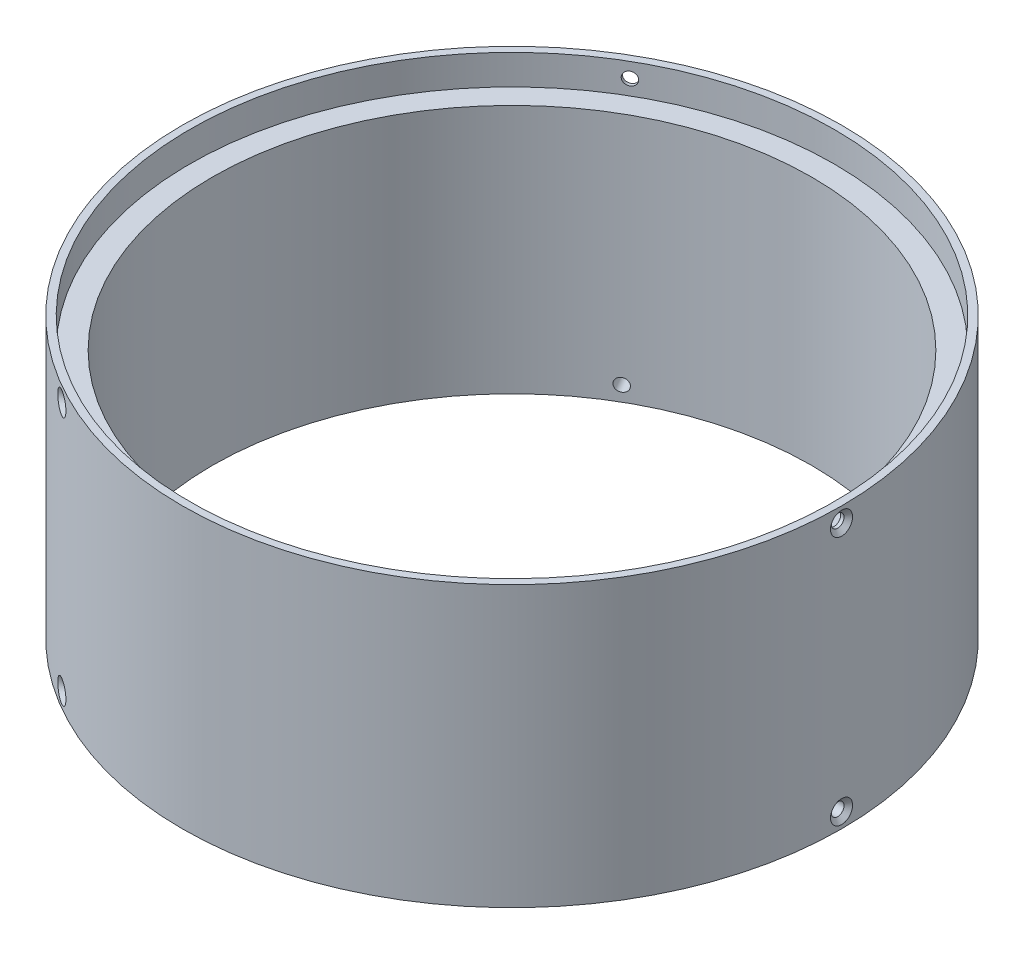
SolidWorks part; units mm, degrees
ref_plane "Front" through (0, 0, 0) normal (0, 0, 1) x (1, 0, 0)
ref_plane "Top" through (0, 0, 0) normal (0, 1, 0) x (1, 0, 0)
ref_plane "Right" through (0, 0, 0) normal (1, 0, 0) x (0, 0, -1)
sketch "Sketch1" plane through (0, 0, 0) normal (0, 0, 1) x (1, 0, 0)
  line L0 (0, 0) -> (0, 73.2721) construction
  line L1 (-83.82, 0) -> (-81.9404, 0)
  line L2 (-81.9404, 0) -> (-81.9404, -7.62)
  line L3 (-81.9404, -7.62) -> (-76.2, -7.62)
  line L4 (-76.2, -7.62) -> (-76.2, -71.12)
  line L5 (-76.2, -71.12) -> (-83.82, -71.12)
  line L6 (-83.82, -71.12) -> (-83.82, 0)
  dimension "D1" = 76.2
  dimension "D2" = 7.62
  dimension "D3" = 63.5
  dimension "D4" = 1.8796
  dimension "D5" = 83.82
revolve "Revolve1" add sketch "Sketch1" angle 360 about L0
hole_wizard "CSK for #4 Flat Head Machine Screw (100)1" positions "3DSketch1" profile "Sketch2" countersink size "#4" standard "ANSI Inch" end condition up to next
sketch3d "3DSketch1"
  point P0 (83.82, -3.81, 0)
  dimension "D1" = 3.81
sketch "Sketch2" plane through (83.82, -3.81, 0) normal (0, 1, 0) x (0, 0, -1)
  line L0 (0, 0) -> (0, 167.64)
  line L1 (0, 167.64) -> (1.6319, 167.64)
  line L2 (1.6319, 167.64) -> (1.6319, 1.0284)
  line L3 (1.6319, 1.0284) -> (2.8575, 0)
  line L5 (2.8575, 0) -> (0, 0)
  line L6 (-1.6319, 1.0284) -> (-2.8575, 0) construction
  line L11 (0, -6.35) -> (0, 107.95) construction
  dimension "Thru Hole Dia." = 3.2639
  dimension "Thru Hole Depth" = 167.64
  dimension "Near C'Sink Dia." = 5.715
  dimension "Near C'Sink Angle" = 100
hole_wizard "CSK for #4 Flat Head Machine Screw (100)2" positions "3DSketch2" profile "Sketch3" countersink size "#4" standard "ANSI Inch" end condition up to next
sketch3d "3DSketch2"
  point P0 (83.82, -67.31, 0)
  dimension "D1" = 3.81
sketch "Sketch3" plane through (83.82, -67.31, 0) normal (0, 1, 0) x (0, 0, -1)
  line L0 (0, 0) -> (0, 167.64)
  line L1 (0, 167.64) -> (1.6319, 167.64)
  line L2 (1.6319, 167.64) -> (1.6319, 1.0284)
  line L3 (1.6319, 1.0284) -> (2.8575, 0)
  line L5 (2.8575, 0) -> (0, 0)
  line L6 (-1.6319, 1.0284) -> (-2.8575, 0) construction
  line L11 (0, -6.35) -> (0, 107.95) construction
  dimension "Thru Hole Dia." = 3.2639
  dimension "Thru Hole Depth" = 167.64
  dimension "Near C'Sink Dia." = 5.715
  dimension "Near C'Sink Angle" = 100
pattern_circular "CirPattern1" count 3 over 360 about axis through (0, 0, 0) along (0, -1, 0) of "CSK for #4 Flat Head Machine Screw (100)2", "CSK for #4 Flat Head Machine Screw (100)1"
